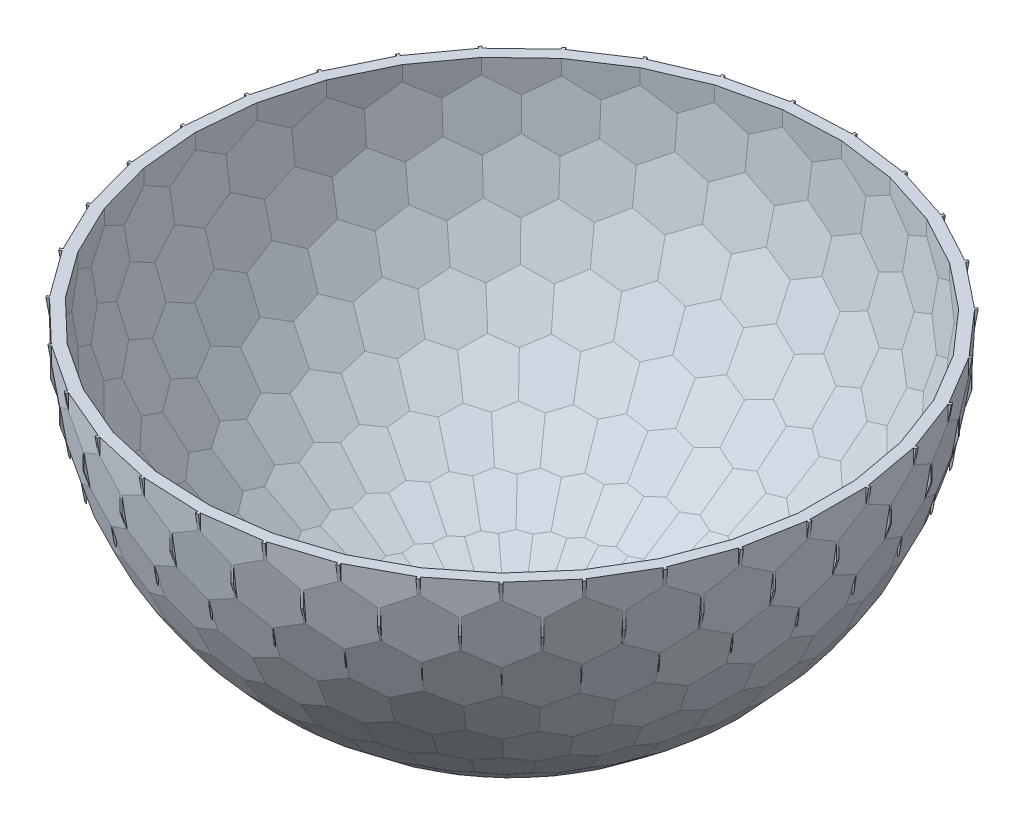
SolidWorks part; units mm, degrees
ref_plane "前视基准面" through (0, 0, 0) normal (0, 0, 1) x (1, 0, 0)
ref_plane "上视基准面" through (0, 0, 0) normal (0, 1, 0) x (1, 0, 0)
ref_plane "右视基准面" through (0, 0, 0) normal (1, 0, 0) x (0, 0, -1)
sketch "草图1" plane through (0, 0, 0) normal (0, 0, 1) x (1, 0, 0)
  line L0 (0, 0) -> (60, 0)
  line L1 (0, 0) -> (0, -59.3971)
  line L2 (0, -59.3971) -> (8.4841, -59.3971)
  arc A0 (8.4841, -59.3971) -> (60, 0) centre (0, 0) ccw
  dimension "D1" = 120
revolve "旋转1" add sketch "草图1" angle 360 about L1
sketch "草图2" plane through (0, 0, 0) normal (0, 0, 1) x (1, 0, 0)
  line L0 (60, 0) -> (-60, 0) construction
  line L1 (58, -8.7421) -> (58, 8.7421)
  line L2 (58, 8.7421) -> (52.8464, 25.4495)
  line L3 (52.8464, 25.4495) -> (42.9973, 39.8956)
  line L4 (42.9973, 39.8956) -> (29.3276, 50.7968)
  line L5 (29.3276, 50.7968) -> (13.052, 57.1845)
  line L6 (13.052, 57.1845) -> (-4.3833, 58.4911)
  line L7 (-4.3833, 58.4911) -> (-21.4291, 54.6005)
  line L8 (-21.4291, 54.6005) -> (-36.5709, 45.8584)
  line L9 (-36.5709, 45.8584) -> (-48.4631, 33.0416)
  line L10 (-48.4631, 33.0416) -> (-56.0492, 17.2889)
  line L11 (-56.0492, 17.2889) -> (-58.6551, 0)
  line L12 (-58.6551, 0) -> (-56.0492, -17.2889)
  line L13 (-56.0492, -17.2889) -> (-48.4631, -33.0416)
  line L14 (-48.4631, -33.0416) -> (-36.5709, -45.8584)
  line L15 (-36.5709, -45.8584) -> (-21.4291, -54.6005)
  line L16 (-21.4291, -54.6005) -> (-4.3833, -58.4911)
  line L17 (-4.3833, -58.4911) -> (13.052, -57.1845)
  line L18 (13.052, -57.1845) -> (29.3276, -50.7968)
  line L19 (29.3276, -50.7968) -> (42.9973, -39.8956)
  line L20 (42.9973, -39.8956) -> (52.8464, -25.4495)
  line L21 (52.8464, -25.4495) -> (58, -8.7421)
  circle A0 centre (0, 0) radius 58 construction
  point P1 (0, 0)
extrude "切除-拉伸2" cut sketch "草图2" against normal mid plane 10 flip side to cut
pattern_circular "阵列(圆周)2" count 35 over 360 about axis through (0, 0, 0) along (0, 1, 0) of "切除-拉伸2"
shell "抽壳1" thickness 2 removed face at (0, 0, 0)
